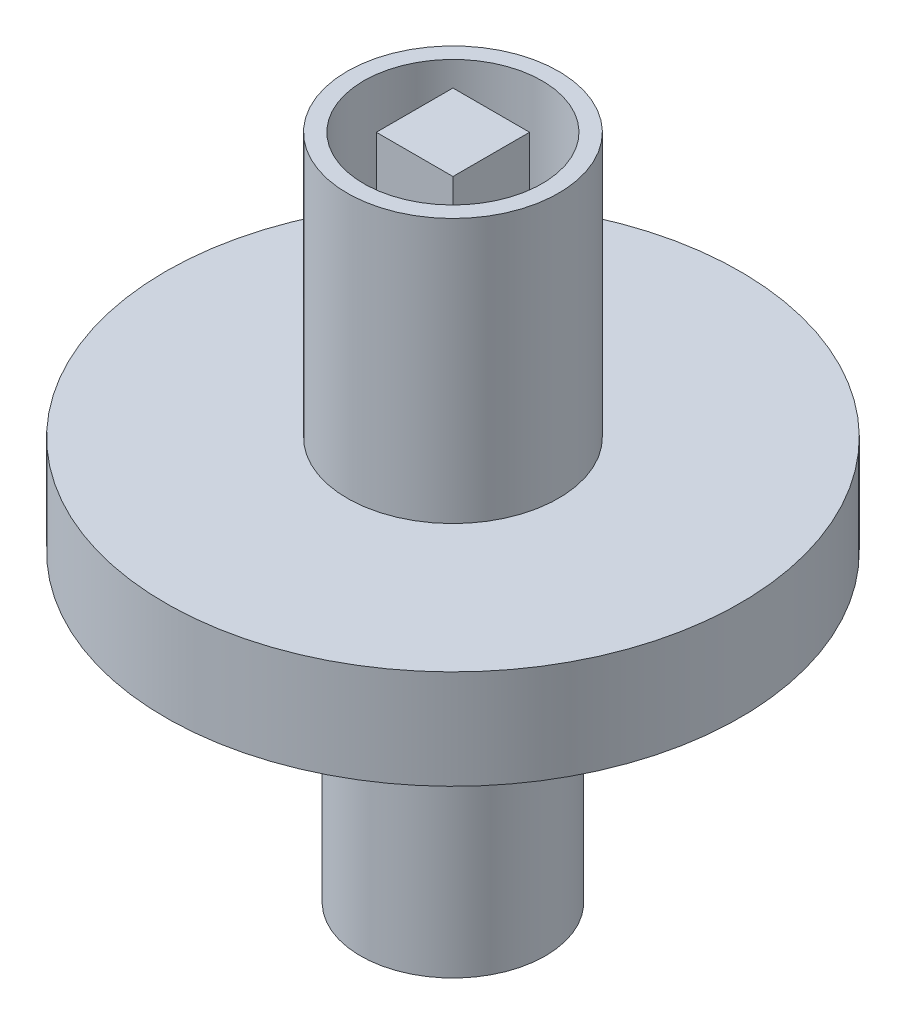
SolidWorks part; units mm, degrees
material "PVC Rigid"
ref_plane "Front Plane" through (0, 0, 0) normal (0, 0, 1) x (1, 0, 0)
ref_plane "Top Plane" through (0, 0, 0) normal (0, 1, 0) x (1, 0, 0)
ref_plane "Right Plane" through (0, 0, 0) normal (1, 0, 0) x (0, 0, -1)
sketch "Sketch1" plane through (0, 0, 0) normal (0, 0, 1) x (1, 0, 0)
  line L0 (0, 96.2797) -> (0, -99.3784) construction
  line L1 (-49.1359, 0) -> (108.8957, 0) construction
sketch "Sketch2" plane through (0, 0, 0) normal (0, 0, 1) x (1, 0, 0)
  line L0 (-49.1359, 0) -> (108.8957, 0) construction
  line L1 (21.75, 0) -> (21.75, 7.5)
  line L2 (21.75, 7.5) -> (8, 7.5)
  line L3 (8, 7.5) -> (8, 27.5)
  line L4 (8, 27.5) -> (0, 27.5)
  line L5 (0, 96.2797) -> (0, -99.3784) construction
  line L6 (0, 27.5) -> (0, 0)
  line L7 (0, 0) -> (21.75, 0)
  dimension "D1" = 21.75
  dimension "D2" = 8
  dimension "D3" = 7.5
  dimension "D4" = 20
revolve "Revolve2" add sketch "Sketch2" angle 360 about L0
sketch "Sketch3" plane through (0, 27.5, 0) normal (0, 1, 0) x (1, 0, 0)
  circle A0 centre (0, 0) radius 6.75
  dimension "D1" = 13.5
extrude "Cut-Extrude1" cut sketch "Sketch3" against normal blind 15 contours A0
sketch "Sketch4" plane through (0, 12.5, 0) normal (0, 1, 0) x (1, 0, 0)
  line L1 (-2.8952, 2.8974) -> (2.9048, 2.8974)
  line L2 (-2.8952, 2.8974) -> (-2.8952, -2.9026)
  line L3 (-2.8952, -2.9026) -> (2.9048, -2.9026)
  line L4 (2.9048, 2.8974) -> (2.9048, -2.9026)
  point P4 (0, 0)
  point P6 (0.0048, -0.0026)
  point P7 (0, 0)
  point P9 (0, 0)
extrude "Boss-Extrude1" add sketch "Sketch4" along normal blind 15
sketch "Sketch6" plane through (0, 0, 0) normal (0, -1, 0) x (1, 0, 0)
  circle A0 centre (0, 0) radius 7
  dimension "D1" = 14
extrude "Boss-Extrude2" add sketch "Sketch6" along normal blind 23
sketch "Sketch7" plane through (0, -23, 0) normal (0, -1, 0) x (1, 0, 0)
  circle A0 centre (0, 0) radius 3.5
  dimension "D1" = 7
extrude "Cut-Extrude2" cut sketch "Sketch7" against normal blind 15
sketch "Sketch8" plane through (0, -23, 0) normal (0, -1, 0) x (1, 0, 0)
  line L4 (-5.3, 1.5) -> (-1.5, 1.5)
  line L5 (-5.3, 1.5) -> (-5.3, -1.5)
  line L6 (5.3, 1.5) -> (5.3, -1.5)
  line L7 (-5.3, -1.5) -> (-1.5, -1.5)
  line L8 (-1.5, -5.3) -> (-1.5, -1.5)
  line L9 (-1.5, -5.3) -> (1.5, -5.3)
  line L10 (-1.5, 5.3) -> (1.5, 5.3)
  line L11 (1.5, -5.3) -> (1.5, -1.5)
  line L12 (1.5, 1.5) -> (5.3, 1.5)
  line L13 (1.5, 1.5) -> (1.5, 5.3)
  line L14 (1.5, -1.5) -> (5.3, -1.5)
  line L15 (-1.5, 1.5) -> (-1.5, 5.3)
  point P1 (0, 0)
  point P2 (0, 0)
  point P3 (0, 0)
  dimension "D1" = 10.6
  dimension "D2" = 3
  dimension "D3" = 10.6
  dimension "D4" = 3
extrude "Cut-Extrude3" cut sketch "Sketch8" against normal blind 15
equation "\"D1@Sketch2\"=43.5/2"
